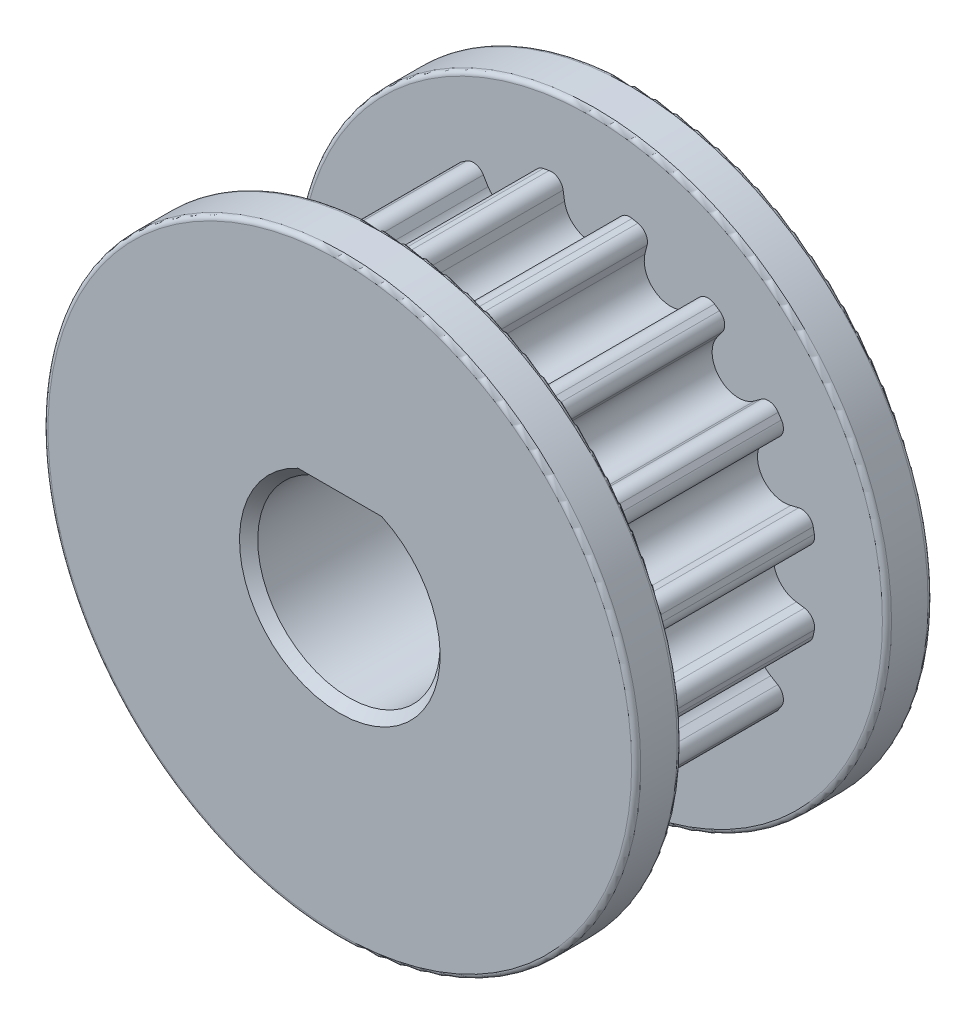
SolidWorks part; units mm, degrees
ref_plane "前视基准面" through (0, 0, 0) normal (0, 0, 1) x (1, 0, 0)
ref_plane "上视基准面" through (0, 0, 0) normal (0, 1, 0) x (1, 0, 0)
ref_plane "右视基准面" through (0, 0, 0) normal (1, 0, 0) x (0, 0, -1)
sketch "草图1" plane through (0, 0, 0) normal (0, 0, 1) x (1, 0, 0)
  line L0 (0, 5.5357) -> (0, 0) construction
  line L1 (0, 0) -> (0.994, 4.9971) construction
  line L2 (-0.8955, 4.5018) -> (0, 0) construction
  line L3 (0.9735, 4.8941) -> (1.0374, 4.8814)
  line L4 (2.3511, 4.1035) -> (2.2586, 3.9502)
  line L5 (2.7723, 4.149) -> (2.7181, 4.1852)
  line L6 (1.2391, 4.5641) -> (1.1909, 4.3689)
  line L7 (2.7723, 4.149) -> (2.8264, 4.1128)
  line L8 (3.7425, 2.8914) -> (3.5984, 2.7852)
  line L9 (4.149, 2.7723) -> (4.1128, 2.8264)
  line L10 (2.8914, 3.7425) -> (2.7722, 3.5806)
  line L11 (4.149, 2.7723) -> (4.1852, 2.7181)
  line L12 (4.5641, 1.2391) -> (4.3903, 1.1962)
  line L13 (4.8941, 0.9735) -> (4.8814, 1.0374)
  line L14 (4.1035, 2.3511) -> (3.9314, 2.2472)
  line L15 (4.8941, 0.9735) -> (4.9068, 0.9096)
  line L16 (4.6908, -0.6018) -> (4.5139, -0.575)
  line L17 (4.8941, -0.9735) -> (4.9068, -0.9096)
  line L18 (4.6908, 0.6018) -> (4.4921, 0.5717)
  line L19 (0.994, 4.9971) -> (1.3866, 6.9711) construction
  line L20 (-0.8955, 4.5018) -> (-1.4, 7.038) construction
  line L21 (-0.9735, 4.8941) -> (-0.9096, 4.9068)
  line L22 (0.6018, 4.6908) -> (0.575, 4.5139)
  line L23 (0.9735, 4.8941) -> (0.9096, 4.9068)
  line L24 (-0.6018, 4.6908) -> (-0.5717, 4.4921)
  line L25 (4.8941, -0.9735) -> (4.8814, -1.0374)
  line L26 (4.1035, -2.3511) -> (3.9502, -2.2586)
  line L27 (4.149, -2.7723) -> (4.1852, -2.7181)
  line L28 (4.5641, -1.2391) -> (4.3689, -1.1909)
  line L29 (4.149, -2.7723) -> (4.1128, -2.8264)
  line L30 (2.8914, -3.7425) -> (2.7852, -3.5984)
  line L31 (2.7723, -4.149) -> (2.8264, -4.1128)
  line L32 (3.7425, -2.8914) -> (3.5806, -2.7722)
  line L33 (2.7723, -4.149) -> (2.7181, -4.1852)
  line L34 (1.2391, -4.5641) -> (1.1962, -4.3903)
  line L35 (0.9735, -4.8941) -> (1.0374, -4.8814)
  line L36 (2.3511, -4.1035) -> (2.2472, -3.9314)
  line L37 (0.9735, -4.8941) -> (0.9096, -4.9068)
  line L38 (-0.6018, -4.6908) -> (-0.575, -4.5139)
  line L39 (-0.9735, -4.8941) -> (-0.9096, -4.9068)
  line L40 (0.6018, -4.6908) -> (0.5717, -4.4921)
  line L41 (-0.9735, -4.8941) -> (-1.0374, -4.8814)
  line L42 (-2.3511, -4.1035) -> (-2.2586, -3.9502)
  line L43 (-2.7723, -4.149) -> (-2.7181, -4.1852)
  line L44 (-1.2391, -4.5641) -> (-1.1909, -4.3689)
  line L45 (-2.7723, -4.149) -> (-2.8264, -4.1128)
  line L46 (-3.7425, -2.8914) -> (-3.5984, -2.7852)
  line L47 (-4.149, -2.7723) -> (-4.1128, -2.8264)
  line L48 (-2.8914, -3.7425) -> (-2.7722, -3.5806)
  line L49 (-4.149, -2.7723) -> (-4.1852, -2.7181)
  line L50 (-4.5641, -1.2391) -> (-4.3903, -1.1962)
  line L51 (-4.8941, -0.9735) -> (-4.8814, -1.0374)
  line L52 (-4.1035, -2.3511) -> (-3.9314, -2.2472)
  line L53 (-4.8941, -0.9735) -> (-4.9068, -0.9096)
  line L54 (-4.6908, 0.6018) -> (-4.5139, 0.575)
  line L55 (-4.8941, 0.9735) -> (-4.9068, 0.9096)
  line L56 (-4.6908, -0.6018) -> (-4.4921, -0.5717)
  line L57 (-4.8941, 0.9735) -> (-4.8814, 1.0374)
  line L58 (-4.1035, 2.3511) -> (-3.9502, 2.2586)
  line L59 (-4.149, 2.7723) -> (-4.1852, 2.7181)
  line L60 (-4.5641, 1.2391) -> (-4.3689, 1.1909)
  line L61 (-4.149, 2.7723) -> (-4.1128, 2.8264)
  line L62 (-2.8914, 3.7425) -> (-2.7852, 3.5984)
  line L63 (-2.7723, 4.149) -> (-2.8264, 4.1128)
  line L64 (-3.7425, 2.8914) -> (-3.5806, 2.7722)
  line L65 (-2.7723, 4.149) -> (-2.7181, 4.1852)
  line L66 (-1.2391, 4.5641) -> (-1.1962, 4.3903)
  line L67 (-0.9735, 4.8941) -> (-1.0374, 4.8814)
  line L68 (-2.3511, 4.1035) -> (-2.2472, 3.9314)
  circle A0 centre (0, 0) radius 4.99 construction
  circle A1 centre (0, 0) radius 4.59 construction
  arc A2 (-0.5717, 4.4921) -> (0.575, 4.5139) centre (0, 4.59) ccw
  arc A3 (-0.6018, 4.6908) -> (-0.9096, 4.9068) centre (-0.8589, 4.6518) ccw
  arc A4 (0.6018, 4.6908) -> (0.9096, 4.9068) centre (0.8589, 4.6518) cw
  arc A5 (1.1909, 4.3689) -> (2.2586, 3.9502) centre (1.7565, 4.2406) ccw
  arc A6 (1.2391, 4.5641) -> (1.0374, 4.8814) centre (0.9867, 4.6264) ccw
  arc A7 (2.3511, 4.1035) -> (2.7181, 4.1852) centre (2.5737, 3.969) cw
  arc A8 (2.7722, 3.5806) -> (3.5984, 2.7852) centre (3.2456, 3.2456) ccw
  arc A9 (2.8914, 3.7425) -> (2.8264, 4.1128) centre (2.682, 3.8967) ccw
  arc A10 (3.7425, 2.8914) -> (4.1128, 2.8264) centre (3.8967, 2.682) cw
  arc A11 (3.9314, 2.2472) -> (4.3903, 1.1962) centre (4.2406, 1.7565) ccw
  arc A12 (4.1035, 2.3511) -> (4.1852, 2.7181) centre (3.969, 2.5737) ccw
  arc A13 (4.5641, 1.2391) -> (4.8814, 1.0374) centre (4.6264, 0.9867) cw
  arc A14 (4.4921, 0.5717) -> (4.5139, -0.575) centre (4.59, 0) ccw
  arc A15 (4.6908, 0.6018) -> (4.9068, 0.9096) centre (4.6518, 0.8589) ccw
  arc A16 (4.6908, -0.6018) -> (4.9068, -0.9096) centre (4.6518, -0.8589) cw
  arc A17 (4.3689, -1.1909) -> (3.9502, -2.2586) centre (4.2406, -1.7565) ccw
  arc A18 (4.5641, -1.2391) -> (4.8814, -1.0374) centre (4.6264, -0.9867) ccw
  arc A19 (4.1035, -2.3511) -> (4.1852, -2.7181) centre (3.969, -2.5737) cw
  arc A20 (3.5806, -2.7722) -> (2.7852, -3.5984) centre (3.2456, -3.2456) ccw
  arc A21 (3.7425, -2.8914) -> (4.1128, -2.8264) centre (3.8967, -2.682) ccw
  arc A22 (2.8914, -3.7425) -> (2.8264, -4.1128) centre (2.682, -3.8967) cw
  arc A23 (2.2472, -3.9314) -> (1.1962, -4.3903) centre (1.7565, -4.2406) ccw
  arc A24 (2.3511, -4.1035) -> (2.7181, -4.1852) centre (2.5737, -3.969) ccw
  arc A25 (1.2391, -4.5641) -> (1.0374, -4.8814) centre (0.9867, -4.6264) cw
  arc A26 (0.5717, -4.4921) -> (-0.575, -4.5139) centre (0, -4.59) ccw
  arc A27 (0.6018, -4.6908) -> (0.9096, -4.9068) centre (0.8589, -4.6518) ccw
  arc A28 (-0.6018, -4.6908) -> (-0.9096, -4.9068) centre (-0.8589, -4.6518) cw
  arc A29 (-1.1909, -4.3689) -> (-2.2586, -3.9502) centre (-1.7565, -4.2406) ccw
  arc A30 (-1.2391, -4.5641) -> (-1.0374, -4.8814) centre (-0.9867, -4.6264) ccw
  arc A31 (-2.3511, -4.1035) -> (-2.7181, -4.1852) centre (-2.5737, -3.969) cw
  arc A32 (-2.7722, -3.5806) -> (-3.5984, -2.7852) centre (-3.2456, -3.2456) ccw
  arc A33 (-2.8914, -3.7425) -> (-2.8264, -4.1128) centre (-2.682, -3.8967) ccw
  arc A34 (-3.7425, -2.8914) -> (-4.1128, -2.8264) centre (-3.8967, -2.682) cw
  arc A35 (-3.9314, -2.2472) -> (-4.3903, -1.1962) centre (-4.2406, -1.7565) ccw
  arc A36 (-4.1035, -2.3511) -> (-4.1852, -2.7181) centre (-3.969, -2.5737) ccw
  arc A37 (-4.5641, -1.2391) -> (-4.8814, -1.0374) centre (-4.6264, -0.9867) cw
  arc A38 (-4.4921, -0.5717) -> (-4.5139, 0.575) centre (-4.59, 0) ccw
  arc A39 (-4.6908, -0.6018) -> (-4.9068, -0.9096) centre (-4.6518, -0.8589) ccw
  arc A40 (-4.6908, 0.6018) -> (-4.9068, 0.9096) centre (-4.6518, 0.8589) cw
  arc A41 (-4.3689, 1.1909) -> (-3.9502, 2.2586) centre (-4.2406, 1.7565) ccw
  arc A42 (-4.5641, 1.2391) -> (-4.8814, 1.0374) centre (-4.6264, 0.9867) ccw
  arc A43 (-4.1035, 2.3511) -> (-4.1852, 2.7181) centre (-3.969, 2.5737) cw
  arc A44 (-3.5806, 2.7722) -> (-2.7852, 3.5984) centre (-3.2456, 3.2456) ccw
  arc A45 (-3.7425, 2.8914) -> (-4.1128, 2.8264) centre (-3.8967, 2.682) ccw
  arc A46 (-2.8914, 3.7425) -> (-2.8264, 4.1128) centre (-2.682, 3.8967) cw
  arc A47 (-2.2472, 3.9314) -> (-1.1962, 4.3903) centre (-1.7565, 4.2406) ccw
  arc A48 (-2.3511, 4.1035) -> (-2.7181, 4.1852) centre (-2.5737, 3.969) ccw
  arc A49 (-1.2391, 4.5641) -> (-1.0374, 4.8814) centre (-0.9867, 4.6264) cw
  point P188 (0, 0)
  dimension "D1" = 9.18
  dimension "D2" = 1.16
  dimension "D4" = 0.52
  dimension "D3" = 16
  dimension "D5" = 0.4
extrude "凸台-拉伸3" add sketch "草图1" along normal blind 4.5
sketch "草图5" plane through (0, 0, 4.5) normal (0, 0, 1) x (1, 0, 0)
  circle A0 centre (0, 0) radius 6.5
  dimension "D1" = 13
extrude "凸台-拉伸4" add sketch "草图5" along normal blind 1
extrude "凸台-拉伸6" add sketch "草图5<2>" against normal blind 1 from offset 4.5 offset against normal yes
sketch "草图5<2>" plane through (0, 0, 4.5) normal (0, 0, 1) x (1, 0, 0) same geometry as "草图5"
sketch "草图6" plane through (0, 0, 5.5) normal (0, 0, 1) x (1, 0, 0)
  line L0 (-0.8718, 1.8) -> (0.8718, 1.8)
  arc A0 (-0.8718, 1.8) -> (0.8718, 1.8) centre (0, 0) ccw
  dimension "D1" = 1.8
  dimension "D2" = 2
extrude "切除-拉伸1" cut sketch "草图6" against normal up to next
chamfer "倒角1" distance 0.2 angle 45 4 edges at (0, 1.8, -1) (0, -2, -1) (0, 1.8, 5.5) (0, -2, 5.5)
fillet "圆角1" radius 0.1 4 edges at (6.5, 0, -1) (6.5, 0, 0) (6.5, 0, 4.5) (6.5, 0, 5.5)
